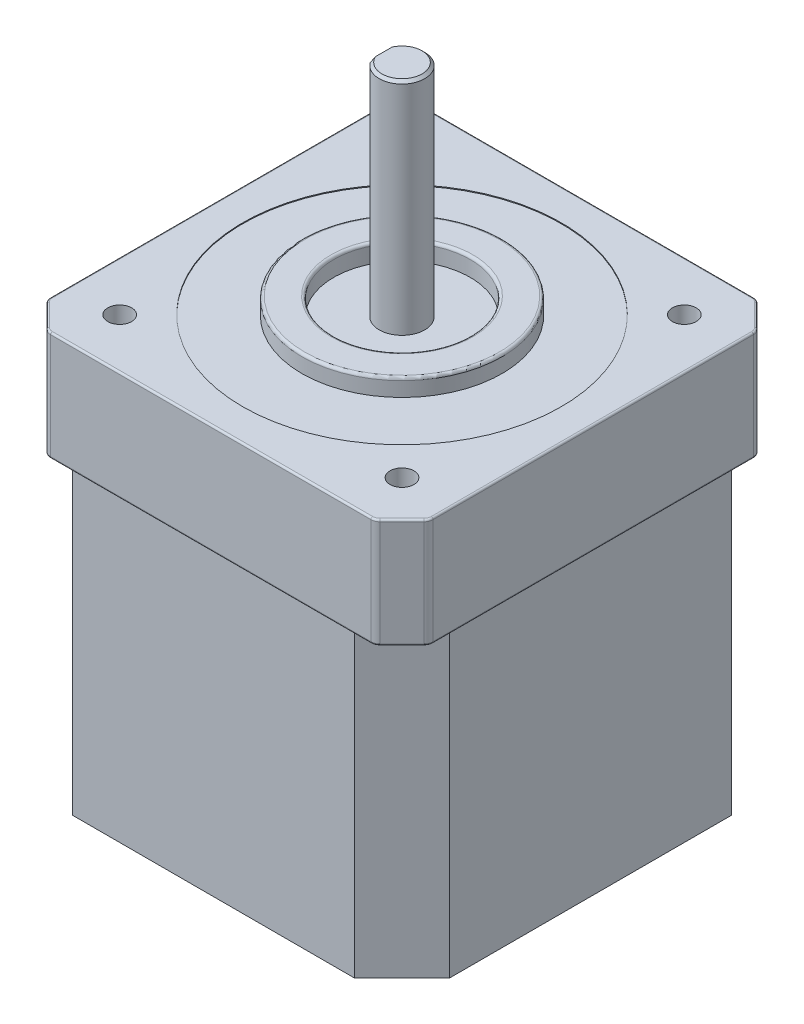
SolidWorks part; units mm, degrees
ref_plane "前视基准面" through (0, 0, 0) normal (0, 0, 1) x (1, 0, 0)
ref_plane "上视基准面" through (0, 0, 0) normal (0, 1, 0) x (1, 0, 0)
ref_plane "右视基准面" through (0, 0, 0) normal (1, 0, 0) x (0, 0, -1)
sketch "草图13" plane through (0, 0, 0) normal (0, 0, 1) x (1, 0, 0)
  line L0 (0, 0) -> (0, 60) construction
  dimension "L" = 60
sketch "草图1" plane through (0, 0, 0) normal (0, 1, 0) x (1, 0, 0)
  line L0 (0, 21) -> (0, -21) construction
  line L1 (-21, 21) -> (21, 21)
  line L2 (-21, 21) -> (-21, -21)
  line L3 (-21, -21) -> (21, -21)
  line L4 (21, 21) -> (21, -21)
  line L5 (-21, 0) -> (21, 0) construction
  dimension "D2" = 21
  dimension "W2" = 42
  dimension "D4" = 21
extrude "凸台-拉伸1" add sketch "草图1" along normal blind 60
chamfer "倒角3" distance 3 angle 45 4 edges at (21, 30, -21) (21, 30, 21) (-21, 30, 21) (-21, 30, -21)
sketch "草图2" plane through (0, 60, 0) normal (0, 1, 0) x (1, 0, 0)
  circle A0 centre (0, 0) radius 11
  dimension "E6" = 22
extrude "凸台-拉伸2" add sketch "草图2" along normal blind 1.8
ref_plane "基准面1" through (0, 12, 0) normal (0, -1, 0) x (1, 0, 0)
sketch "草图3" plane through (0, 60, 0) normal (0, 1, 0) x (1, 0, 0)
  line L0 (-2, 1.5) -> (-2, -1.5) construction
  circle A0 centre (0, 0) radius 2.5
  point P3 (2.5, 0)
  dimension "D1" = 4.5
  dimension "E4" = 5
extrude "凸台-拉伸3" add sketch "草图3" along normal blind 24
sketch "草图4" plane through (0, 12, 0) normal (0, -1, 0) x (1, 0, 0)
  line L0 (15.4716, 20.7) -> (-15.4716, 20.7)
  line L1 (-15.4716, 20.7) -> (-20.7, 15.4716)
  line L2 (-20.7, 15.4716) -> (-20.7, -15.4716)
  line L3 (-20.7, -15.4716) -> (-15.4716, -20.7)
  line L4 (-15.4716, -20.7) -> (15.4716, -20.7)
  line L5 (15.4716, -20.7) -> (20.7, -15.4716)
  line L6 (20.7, -15.4716) -> (20.7, 15.4716)
  line L7 (20.7, 15.4716) -> (15.4716, 20.7)
  line L8 (18, -21) -> (-18, -21) construction
  line L9 (-21, -18) -> (-21, 18) construction
  line L10 (21, 18) -> (21, -18) construction
  line L11 (-18, 21) -> (18, 21) construction
  line L15 (-18, 21) -> (-21, 18) construction
  line L21 (0, -21) -> (0, 21) construction
  line L22 (0, -21) -> (0, 21) construction
  line L23 (-21, 0) -> (21, 0) construction
  dimension "D1" = 0.3
  dimension "D2" = 0.3
  dimension "D3" = 0.3
  dimension "D4" = 0.3
  dimension "D5" = 2
extrude "切除-拉伸1" cut sketch "草图4" against normal blind 36 flip side to cut
fillet "圆角2" radius 1 16 edges at (21, 6, 18) (18, 6, 21) (-18, 6, 21) (-21, 6, 18) (21, 6, -18) (18, 6, -21) (-18, 6, -21) (-21, 6, -18) (-18, 54, -21) (-21, 54, -18) (21, 54, -18) (18, 54, -21) (21, 54, 18) (18, 54, 21) (-18, 54, 21) (-21, 54, 18)
fillet "圆角3" radius 0.2 64 edges at (-21, 48, 0) (-20.9239, 48, 17.9685) (0, 48, 21) (-17.9685, 48, 20.9239) (0, 12, 21) (17.9685, 12, 20.9239) (21, 12, 0) (20.9239, 12, 17.9685) (17.9685, 48, 20.9239) (21, 48, 0) (20.9239, 48, 17.9685) (-21, 12, 0) (-20.9239, 12, 17.9685) (-17.9685, 12, 20.9239) (0, 12, -21) (-17.9685, 12, -20.9239) (-20.9239, 12, -17.9685) (0, 48, -21) (-17.9685, 48, -20.9239) (-20.9239, 48, -17.9685) (-20.9239, 60, -17.9685) (-19.5, 60, -19.5) (-17.9685, 60, -20.9239) (0, 60, -21) (17.9685, 60, -20.9239) (19.5, 60, -19.5) (20.9239, 60, -17.9685) (21, 60, 0) (20.9239, 60, 17.9685) (19.5, 60, 19.5) (17.9685, 60, 20.9239) (0, 60, 21) (-17.9685, 60, 20.9239) (-20.9239, 60, 17.9685) (-20.9239, 0, -17.9685) (-21, 0, 0) (-20.9239, 0, 17.9685) (-19.5, 0, 19.5) (-17.9685, 0, 20.9239) (0, 0, 21) (17.9685, 0, 20.9239) (19.5, 0, 19.5) (20.9239, 0, 17.9685) (21, 0, 0) (20.9239, 0, -17.9685) (19.5, 0, -19.5) (17.9685, 0, -20.9239) (0, 0, -21) (-17.9685, 0, -20.9239) (-19.5, 60, 19.5) (-19.5, 48, 19.5) (19.5, 12, 19.5) (19.5, 48, 19.5) (-19.5, 12, 19.5) (-19.5, 12, -19.5) (-19.5, 48, -19.5) (-21, 60, 0) (-19.5, 0, -19.5) (17.9685, 12, -20.9239) (19.5, 12, -19.5) (20.9239, 12, -17.9685) (17.9685, 48, -20.9239) (19.5, 48, -19.5) (20.9239, 48, -17.9685)
sketch "草图14" plane through (0, 84, 0) normal (0, 1, 0) x (1, 0, 0)
  line L0 (-2, 1.5) -> (-2, -1.5) construction
  line L1 (-2, 1.5) -> (-2, -1.5)
  circle A1 centre (0, 0) radius 2.5 construction
  arc A2 (-2, 1.5) -> (-2, -1.5) centre (0, 0) ccw
extrude "切除-拉伸5" cut sketch "草图14" against normal blind 15
chamfer "倒角5" distance 0.3 angle 45 1 edges at (2.5, 84, 0)
chamfer "倒角4" distance 0.5 angle 45 1 edges at (-2, 69, 0)
chamfer "倒角6" [suppressed] distance 1 angle 45
sketch "草图6" plane through (0, 60, 0) normal (0, 1, 0) x (1, 0, 0)
  line L0 (0, 21) -> (0, -21) construction
  line L3 (-21, 0) -> (21, 0) construction
  line L7 (-21, -21) -> (21, -21) construction
  circle A0 centre (-15.5, 15.5) radius 1.3105
  circle A1 centre (15.5, 15.5) radius 1.3105
  circle A2 centre (15.5, -15.5) radius 1.3105
  circle A3 centre (-15.5, -15.5) radius 1.3105
  dimension "D1" = 31
  dimension "E2" = 2.621
  dimension "E1" = 15.5
extrude "切除-拉伸2" cut sketch "草图6" against normal blind 4.5
cosmetic thread "装饰螺纹线1" parameters "D2"=3
cosmetic thread "装饰螺纹线2" parameters "D2"=3
cosmetic thread "装饰螺纹线3" parameters "D2"=3
cosmetic thread "装饰螺纹线4" parameters "D2"=3
sketch "草图7" plane through (0, 61.8, 0) normal (0, 1, 0) x (1, 0, 0)
  circle A0 centre (0, 0) radius 7.5
  circle A1 centre (0, 0) radius 2.5
  dimension "D1" = 15
  dimension "D2" = 5
extrude "切除-拉伸3" cut sketch "草图7" against normal blind 2
sketch "草图8" plane through (21, 0, 0) normal (1, 0, 0) x (0, 0, -1)
  line L0 (0, 12) -> (0, 0) construction
  line L2 (-15.1716, 12) -> (-18, 12) construction
  circle A0 centre (0, 6) radius 4.125
  dimension "D1" = 8.25
extrude "凸台-拉伸5" add sketch "草图8" along normal blind 1.2
sketch "草图9" plane through (22.2, 0, 0) normal (1, 0, 0) x (0, 0, -1)
  circle A0 centre (0, 6) radius 2.25
  circle A1 centre (0, 6) radius 2.05
  circle A2 centre (0, 6) radius 4.125 construction
  dimension "D1" = 4.5
  dimension "D2" = 0.2
extrude "凸台-拉伸6" add sketch "草图9" along normal blind 15.4
sketch "草图10" plane through (22.2, 0, 0) normal (1, 0, 0) x (0, 0, -1)
  line L0 (0, 6) -> (-0.9526, 6.55) construction
  line L1 (0, 6) -> (0.9526, 6.55) construction
  line L2 (0, 6) -> (0, 4.9) construction
  circle A0 centre (-0.9526, 6.55) radius 0.65 construction
  circle A1 centre (0.9526, 6.55) radius 0.65
  circle A2 centre (0, 4.9) radius 0.65 construction
  circle A5 centre (0, 6) radius 1.1 construction
  dimension "D1" = 120
  dimension "D2" = 2.2
  dimension "D3" = 1.3
  dimension "D4" = 120
extrude "凸台-拉伸8" add sketch "草图10" along normal blind 15.4 contours A0 | A2 | A1
sketch "草图15" plane through (0, 60, 0) normal (0, 1, 0) x (1, 0, 0)
  circle A0 centre (0, 0) radius 17.5
  circle A1 centre (0, 0) radius 11 construction
  circle A2 centre (0, 0) radius 11
  dimension "D1" = 35
extrude "切除-拉伸6" cut sketch "草图15" against normal blind 0.1
fillet "圆角4" radius 0.3 2 edges at (0, 61.8, 7.5) (0, 61.8, 11)
pattern_circular "阵列(圆周)3" count 4 over 360 about axis through (0, 6, 0) along (1, 0, 0) of "凸台-拉伸8"
sketch "草图16" [suppressed] plane through (0, 0, -20.85) normal (0, 0, -1) x (-1, 0, 0)
  line L0 (0, 36.8) -> (0, 9.2) construction
  line L1 (15.6216, 36.8) -> (-15.6216, 36.8) construction
  line L2 (15.6216, 9.2) -> (-15.6216, 9.2) construction
  line L4 (-12.5, 7.2) -> (12.5, 7.2)
  line L5 (-12.5, 7.2) -> (-12.5, 38.8)
  line L6 (-12.5, 38.8) -> (12.5, 38.8)
  line L7 (12.5, 7.2) -> (12.5, 38.8)
  line L8 (-12.5, 7.2) -> (12.5, 38.8) construction
  line L9 (-12.5, 38.8) -> (12.5, 7.2) construction
  point P6 (0, 23)
  dimension "D1" = 2
  dimension "D2" = 25
extrude "切除-拉伸9" [suppressed] cut sketch "草图16" along normal blind 0.3
sketch "草图17" [suppressed] plane through (0, 0, 20.85) normal (0, 0, 1) x (1, 0, 0)
  line L4 (-12.5, 7.2) -> (12.5, 7.2)
  line L5 (-12.5, 38.8) -> (-12.5, 7.2)
  line L6 (12.5, 38.8) -> (-12.5, 38.8)
  line L7 (12.5, 7.2) -> (12.5, 38.8)
  line L8 (-12.5, 7.2) -> (12.5, 7.2)
  line L9 (-12.5, 38.8) -> (-12.5, 7.2)
  line L10 (12.5, 38.8) -> (-12.5, 38.8)
  line L11 (12.5, 7.2) -> (12.5, 38.8)
  dimension "D1" = 0
extrude "切除-拉伸10" [suppressed] cut sketch "草图17" along normal up to surface (0.3 mm away)
sketch "草图18" [suppressed] plane through (20.85, 0, 0) normal (1, 0, 0) x (0, 0, -1)
  line L0 (0, 9.2) -> (0, 36.8) construction
  line L1 (15.6216, 9.2) -> (-15.6216, 9.2) construction
  line L2 (15.6216, 36.8) -> (-15.6216, 36.8) construction
  line L4 (-12.5, 8.2) -> (12.5, 8.2)
  line L5 (-12.5, 8.2) -> (-12.5, 37.8)
  line L6 (-12.5, 37.8) -> (12.5, 37.8)
  line L7 (12.5, 8.2) -> (12.5, 37.8)
  line L8 (-12.5, 8.2) -> (12.5, 37.8) construction
  line L9 (-12.5, 37.8) -> (12.5, 8.2) construction
  point P6 (0, 23)
  dimension "D1" = 1
  dimension "D2" = 25
extrude "切除-拉伸11" [suppressed] cut sketch "草图18" along normal up to surface (0.3 mm away)
sketch "草图19" [suppressed] plane through (-20.85, 0, 0) normal (-1, 0, 0) x (0, 0, 1)
  line L4 (-12.5, 8.2) -> (12.5, 8.2)
  line L5 (-12.5, 37.8) -> (-12.5, 8.2)
  line L6 (12.5, 37.8) -> (-12.5, 37.8)
  line L7 (12.5, 8.2) -> (12.5, 37.8)
  line L8 (-12.5, 8.2) -> (12.5, 8.2)
  line L9 (-12.5, 37.8) -> (-12.5, 8.2)
  line L10 (12.5, 37.8) -> (-12.5, 37.8)
  line L11 (12.5, 8.2) -> (12.5, 37.8)
  dimension "D1" = 0
extrude "切除-拉伸12" [suppressed] cut sketch "草图19" along normal up to surface (0.3 mm away)
sketch "草图20" plane through (0, 0, 0) normal (0, -1, 0) x (1, 0, 0)
  line L1 (44.1463, 39.9469) -> (-44.1463, 39.9469)
  line L2 (44.1463, 39.9469) -> (44.1463, -39.9469)
  line L3 (44.1463, -39.9469) -> (-44.1463, -39.9469)
  line L4 (-44.1463, 39.9469) -> (-44.1463, -39.9469)
  line L5 (44.1463, 39.9469) -> (-44.1463, -39.9469) construction
  line L6 (44.1463, -39.9469) -> (-44.1463, 39.9469) construction
  point P0 (0, 0)
extrude "切除-拉伸13" cut sketch "草图20" against normal blind 15
